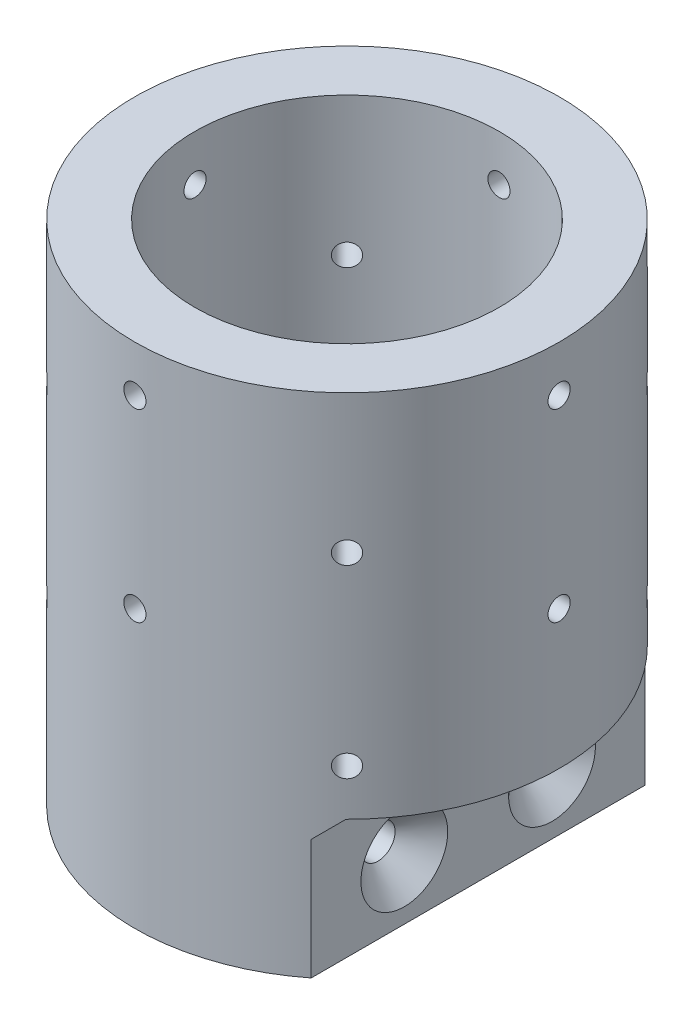
SolidWorks part; units mm, degrees
ref_plane "Спереди" through (0, 0, 0) normal (0, 0, 1) x (1, 0, 0)
ref_plane "Сверху" through (0, 0, 0) normal (0, 1, 0) x (1, 0, 0)
ref_plane "Справа" through (0, 0, 0) normal (1, 0, 0) x (0, 0, -1)
sketch "Эскиз1" plane through (0, 0, 0) normal (0, 1, 0) x (1, 0, 0)
  circle A0 centre (0, 0) radius 23
  dimension "D1" = 46
extrude "Бобышка-Вытянуть1" add sketch "Эскиз1" along normal blind 5
sketch "Эскиз2" plane through (0, 5, 0) normal (0, 1, 0) x (1, 0, 0)
  circle A0 centre (0, 0) radius 23
  circle A1 centre (0, 0) radius 16.5
  circle A2 centre (0, 0) radius 23 construction
  dimension "D1" = 33
  dimension "D2" = 0
extrude "Бобышка-Вытянуть2" add sketch "Эскиз2" along normal blind 35
chamfer "Фаска8" distance 2 angle 45 1 edges at (0, 5, 16.5)
sketch "Эскиз3" plane through (0, 0, 0) normal (1, 0, 0) x (0, 0, -1)
  line L0 (-23, 20) -> (28.0263, 20) construction
  line L1 (-23, 40) -> (-23, 0) construction
  line L2 (16.5, 40) -> (-16.5, 40) construction
  circle A1 centre (0, 35) radius 1.2
  dimension "D1" = 2.4
  dimension "D2" = 5
extrude "Вырез-Вытянуть1" cut sketch "Эскиз3" against normal through all
ref_plane "Плоскость1" through (0, 0, 0) normal (0.7071, 0, 0.7071) x (0, -1, 0)
sketch "Эскиз4" plane through (0, 0, 0) normal (0.7071, 0, 0.7071) x (0, -1, 0)
  line L0 (-20, 23) -> (-20, -30.0625) construction
  line L1 (0, 23) -> (-40, 23) construction
  line L3 (0, -23) -> (0, 23) construction
  circle A1 centre (-5, 0) radius 1.2
  dimension "D1" = 5
  dimension "D2" = 2.4
extrude "Вырез-Вытянуть2" cut sketch "Эскиз4" against normal through all from offset 16.3 offset against normal yes
pattern_circular "Круговой массив1" count 4 over 360 about axis through (0, 5, 0) along (0, -1, 0) of "Вырез-Вытянуть2"
pattern_circular "Круговой массив2" count 4 over 360 about axis through (0, 5, 0) along (0, -1, 0) of "Вырез-Вытянуть1"
pattern_linear "Линейный массив3" count 2 spacing 20 along (0, 1, 0) of "Круговой массив1"
pattern_linear "Линейный массив4" count 2 spacing 20 along (0, -1, 0) of "Круговой массив2"
sketch "Эскиз12" plane through (0, 0, 0) normal (0, -1, 0) x (1, 0, 0)
  line L1 (14.207, 18.0876) -> (14.207, -18.0876)
  line L20 (0, 15) -> (-2.7835, 17.7835)
  line L21 (-2.7835, -17.7835) -> (0, -15)
  line L22 (0, -15) -> (0, 15)
  line L23 (0, 15) -> (-2.7835, 17.7835)
  line L24 (-2.7835, -17.7835) -> (0, -15)
  line L25 (0, -15) -> (0, 15)
  circle A6 centre (0, 0) radius 23 construction
  arc A7 (14.207, 18.0876) -> (14.207, -18.0876) centre (0, 0) ccw
  arc A13 (-2.7835, 17.7835) -> (-2.7835, -17.7835) centre (0, 0) ccw
  arc A14 (-2.7835, 17.7835) -> (-2.7835, -17.7835) centre (0, 0) ccw
  dimension "D1" = 0
extrude "Бобышка-Вытянуть3" add sketch "Эскиз12" along normal blind 15 contours L1 region at (13.6153, 0, 0)
sketch "Эскиз13" plane through (0, -15, 0) normal (0, -1, 0) x (1, 0, 0)
  line L14 (-2.6786, -18.1029) -> (0.3, -15.1243)
  line L15 (0.3, 15.1243) -> (-2.6786, 18.1029)
  line L16 (0.3, -15.1243) -> (0.3, 15.1243)
  line L17 (-2.6786, -18.1029) -> (0.3, -15.1243)
  line L18 (0.3, 15.1243) -> (-2.6786, 18.1029)
  line L19 (0.3, -15.1243) -> (0.3, 15.1243)
  arc A5 (-2.6786, 18.1029) -> (-2.6786, -18.1029) centre (0, 0) ccw
  arc A6 (-2.6786, 18.1029) -> (-2.6786, -18.1029) centre (0, 0) ccw
  dimension "D1" = 0.3
extrude "Вырез-Вытянуть10" cut sketch "Эскиз13" against normal up to surface (15 mm away) up to face at (18.6035, 0, 0)
chamfer "Фаска4" distance 2 angle 45 1 edges at (14.207, 0, 0)
chamfer "Фаска6" distance 2 angle 45 4 edges at (-1.1893, 0, -16.6136) (-18.3, 0, 0) (0.3, 0, 0) (-1.1893, 0, 16.6136)
chamfer "Фаска7" distance 2 angle 45 4 edges at (-1.1893, -15, -16.6136) (-18.3, -15, 0) (-1.1893, -15, 16.6136) (0.3, -15, 0)
hole_wizard "Зенковка для винта с полупотайной головкой M41" positions "Эскиз14" profile "Эскиз15" countersink size "M4" standard "ISO" end condition through all
sketch "Эскиз14" plane through (14.207, -656.2045, -24.0267) normal (1, 0, 0) x (0, 0.0202, -0.9998)
  line L0 (-10.8298, 654.5559) -> (-11.092, 641.5586) construction
  line L4 (-10.9609, 648.0573) -> (-20.4413, 648.0573) construction
  line L5 (-20.4413, 648.0573) -> (-1.8045, 648.0573) construction
  point P0 (-18.9609, 648.0573)
  point P19 (-2.9674, 647.7347)
sketch "Эскиз15" plane through (14.207, -8.6613, 7.9984) normal (0, 1, 0) x (0, 0, -1)
  line L0 (0, 0) -> (0, 37.207)
  line L1 (0, 37.207) -> (1.85, 37.207)
  line L2 (1.85, 37.207) -> (1.85, 2.85)
  line L3 (1.85, 2.85) -> (4.7, 0)
  line L4 (4.7, 0) -> (0, 0)
  line L5 (-1.85, 2.85) -> (-4.7, 0) construction
  line L6 (0, -6.35) -> (0, 107.95) construction
  dimension "Диаметр сквозного отверстия" = 3.7
  dimension "Глубина сквозного отверстия" = 37.207
  dimension "Диаметр передней зенковки" = 9.4
  dimension "Угол передней зенковки" = 90
